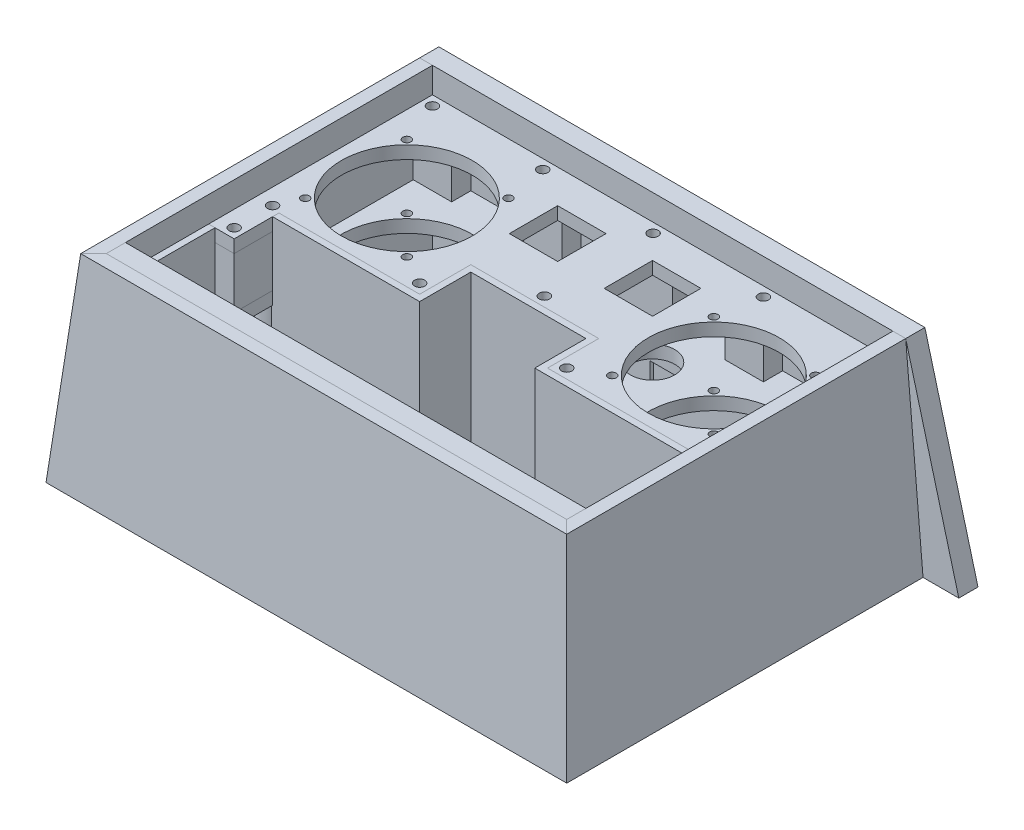
SolidWorks part; units mm, degrees
material "Alum Plate"
ref_plane "Front Plane" through (0, 0, 0) normal (0, 0, 1) x (1, 0, 0)
ref_plane "Top Plane" through (0, 0, 0) normal (0, 1, 0) x (1, 0, 0)
ref_plane "Right Plane" through (0, 0, 0) normal (1, 0, 0) x (0, 0, -1)
other "Center of Mass"
sketch "Sketch1" plane through (0, 0, 0) normal (0, 1, 0) x (1, 0, 0)
  line L0 (-76.2, 25.4) -> (-23.5486, 47.625) construction
  line L1 (114.3, -76.2) -> (-114.3, -76.2)
  line L2 (114.3, -76.2) -> (114.3, 76.2)
  line L3 (114.3, 76.2) -> (-114.3, 76.2)
  line L4 (-114.3, -76.2) -> (-114.3, 76.2)
  line L5 (114.3, -76.2) -> (-114.3, 76.2) construction
  line L6 (114.3, 76.2) -> (-114.3, -76.2) construction
  line L8 (-127, 0) -> (49.8373, 0) construction
  line L9 (0, 0) -> (0, 61.2225) construction
  line L10 (-114.3, -12.7) -> (114.3, -12.7) construction
  line L11 (-111.125, -59.275) -> (-53.975, -59.275)
  line L12 (-111.125, -59.275) -> (-111.125, -23.275)
  line L13 (-111.125, -23.275) -> (-53.975, -23.275)
  line L14 (-53.975, -59.275) -> (-53.975, -23.275)
  line L15 (-111.125, -59.275) -> (-53.975, -23.275) construction
  line L16 (-111.125, -23.275) -> (-53.975, -59.275) construction
  line L17 (-53.975, -55.275) -> (-6.985, -55.275)
  line L18 (-53.975, -55.275) -> (-53.975, -27.275)
  line L19 (-53.975, -27.275) -> (-6.985, -27.275)
  line L20 (-6.985, -55.275) -> (-6.985, -27.275)
  line L21 (-53.975, -55.275) -> (-6.985, -27.275) construction
  line L22 (-53.975, -27.275) -> (-6.985, -55.275) construction
  line L23 (-76.2, -12.7) -> (-76.2, 25.4) construction
  line L24 (-76.2, 25.4) -> (-76.2, 76.2) construction
  circle A0 centre (-76.2, 25.4) radius 32.5
  circle A1 centre (-23.5486, 47.625) radius 10.9728
  point P2 (0, 0)
  point P10 (107.95, -67.76)
  point P11 (-69.85, 31.4275)
  point P15 (-82.55, -41.275)
  point P21 (-76.2, 57.9)
  point P22 (-30.48, -41.275)
  point P27 (-76.2, -7.1)
  point P28 (-23.5486, 36.6522)
  point P29 (-53.975, -41.275)
  point P30 (-23.5486, 58.5978)
  dimension "D1" = 65
  dimension "D6" = 38.1
  dimension "D7" = 21.9456
  dimension "D2" = 50.8
  dimension "D3" = 38.1
  dimension "D4" = 228.6
  dimension "D5" = 63.5
  dimension "D8" = 57.15
  dimension "D10" = 28.575
  dimension "D11" = 36
  dimension "D12" = 57.15
  dimension "D13" = 46.99
  dimension "D14" = 28
  dimension "D15" = 28.575
  dimension "D16" = 3.175
sketch "Sketch2" plane through (0, 0, 0) normal (1, 0, 0) x (0, 0, -1)
  line L0 (-200000, 0) -> (200061.2225, 0) construction
  line L1 (25.4, 50.8) -> (25.4, 53.975) construction
  line L2 (-7.1, 60.975) -> (57.9, 60.975)
  line L3 (-7.1, 60.975) -> (-7.1, 53.975)
  line L4 (-7.1, 53.975) -> (57.9, 53.975)
  line L5 (57.9, 60.975) -> (57.9, 53.975)
  line L6 (-7.1, 60.975) -> (57.9, 53.975) construction
  line L7 (-7.1, 53.975) -> (57.9, 60.975) construction
  line L8 (-7.1, 92.075) -> (57.9, 92.075)
  line L9 (-7.1, 92.075) -> (-7.1, 85.075)
  line L10 (-7.1, 85.075) -> (57.9, 85.075)
  line L11 (57.9, 92.075) -> (57.9, 85.075)
  line L12 (-7.1, 92.075) -> (57.9, 85.075) construction
  line L13 (-7.1, 85.075) -> (57.9, 92.075) construction
  line L14 (23.1368, 73.025) -> (44.1892, 73.025) construction
  line L15 (25.4, 60.975) -> (25.4, 73.025) construction
  line L16 (25.4, 73.025) -> (25.4, 85.075) construction
  line L17 (-59.275, 0) -> (-23.275, 0) construction
  circle A0 centre (25.4, 25.4) radius 25.4
  circle A1 centre (-41.275, 28.575) radius 18
  point P4 (25.4, 57.475)
  point P9 (25.4, 88.575)
  point P26 (-36.2764, 48.644)
  point P27 (0, 0)
  point P30 (-41.275, 0)
  point P31 (-41.275, 28.575)
  dimension "D1" = 50.8
  dimension "D6" = 36
  dimension "D2" = 7
  dimension "D3" = 3.175
  dimension "D4" = 38.1
  dimension "D5" = 25.4
ref_plane "Plane1" through (0, 53.975, 0) normal (0, 1, 0) x (1, 0, 0)
sketch "Sketch3" plane through (0, 53.975, 0) normal (0, 1, 0) x (1, 0, 0)
  line L0 (0, -200000) -> (0, 200061.2225) construction
  line L1 (-114.3, 76.2) -> (0, 76.2)
  line L2 (-114.3, 76.2) -> (-114.3, -12.7)
  line L3 (-114.3, -12.7) -> (0, -12.7)
  line L4 (0, 76.2) -> (0, -12.7)
  line L5 (-114.3, 76.2) -> (0, -12.7) construction
  line L6 (-114.3, -12.7) -> (0, 76.2) construction
  line L7 (-114.3, 25.4) -> (-76.2, 25.4) construction
  line L8 (-114.3, -12.7) -> (114.3, -12.7) construction
  line L9 (-114.3, -76.2) -> (-114.3, 76.2) construction
  circle A0 centre (-76.2, 25.4) radius 32.5 construction
  circle A1 centre (-76.2, 25.4) radius 32.5
  point P7 (-57.15, 31.75)
  point P12 (0, -12.7)
  point P15 (-114.3, 25.4)
extrude "Boss-Extrude1" add sketch "Sketch3" along normal blind 6.35
ref_plane "Plane2" through (0, 73.025, 0) normal (0, 1, 0) x (1, 0, 0)
sketch "Sketch12" plane through (0, 60.325, 0) normal (0, 1, 0) x (1, 0, 0)
  line L0 (-114.3, 76.2) -> (-114.3, -12.7) construction
  line L1 (-114.3, -12.7) -> (-101.6, -12.7)
  line L2 (-114.3, -12.7) -> (-114.3, -34.925)
  line L3 (-114.3, -34.925) -> (-101.6, -34.925)
  line L4 (-101.6, -12.7) -> (-101.6, -34.925)
  line L5 (-114.3, -12.7) -> (-101.6, -34.925) construction
  line L6 (-114.3, -34.925) -> (-101.6, -12.7) construction
  line L7 (-114.3, -12.7) -> (0, -12.7) construction
  point P4 (-107.95, -23.8125)
  point P7 (-101.6, -76.2)
  point P8 (-101.6, -37.9407)
  dimension "D1" = 12.7
  dimension "D2" = 22.225
extrude "Boss-Extrude8" add sketch "Sketch12" against normal up to surface (6.35 mm away) up to face at (-57.15, 53.975, -31.75)
mirror "Mirror1" about plane through (0, 73.025, 0) normal (0, 1, 0) of bodies 128 101
mirror "Mirror2" about plane through (0, 0, 0) normal (1, 0, 0) of bodies 128 102 101 114
sketch "Sketch5" plane through (0, 60.325, 0) normal (0, 1, 0) x (1, 0, 0)
  circle A1 centre (-23.5486, 47.625) radius 10.9728 construction
  circle A3 centre (-23.5486, 47.625) radius 10.9728
  point P6 (0, 25.4)
extrude "Cut-Extrude1" cut sketch "Sketch5" against normal through all
sketch "Sketch47" plane through (0, 92.075, 0) normal (0, 1, 0) x (1, 0, 0)
  line L1 (-35.5486, 59.625) -> (-11.5486, 59.625)
  line L2 (-35.5486, 59.625) -> (-35.5486, 35.625)
  line L3 (-35.5486, 35.625) -> (-11.5486, 35.625)
  line L4 (-11.5486, 59.625) -> (-11.5486, 35.625)
  line L5 (-35.5486, 59.625) -> (-11.5486, 35.625) construction
  line L6 (-35.5486, 35.625) -> (-11.5486, 59.625) construction
  circle A0 centre (-23.5486, 47.625) radius 10.9728 construction
  point P0 (-23.5486, 47.625)
  dimension "D1" = 24
extrude "Cut-Extrude19" cut sketch "Sketch47" against normal up to surface (6.35 mm away)
ref_axis "Axis1" through (0, 60.975, -25.4) along (0, 1, 0)
sketch "Sketch22" plane through (0, 92.075, 0) normal (0, 1, 0) x (1, 0, 0)
  line L0 (-54.1171, 47.4829) -> (-53.219, 48.381) construction
  line L1 (-50.974, 50.626) -> (-101.426, 50.626) construction
  line L2 (-50.974, 50.626) -> (-50.974, 0.174) construction
  line L3 (-50.974, 0.174) -> (-101.426, 0.174) construction
  line L4 (-101.426, 50.626) -> (-101.426, 0.174) construction
  line L5 (-50.974, 50.626) -> (-101.426, 0.174) construction
  line L6 (-50.974, 0.174) -> (-101.426, 50.626) construction
  circle A0 centre (-101.426, 50.626) radius 2.0193
  circle A1 centre (-50.974, 50.626) radius 2.0193
  circle A2 centre (-50.974, 0.174) radius 2.0193
  circle A3 centre (-101.426, 0.174) radius 2.0193
  circle A4 centre (-50.974, 50.626) radius 4.445 construction
  circle A5 centre (-76.2, 25.4) radius 32.5 construction
  point P0 (-76.2, 25.4)
  dimension "D1" = 4.0386
  dimension "D2" = 8.89
  dimension "D3" = 1.27
extrude "Cut-Extrude7" cut sketch "Sketch22" against normal through all
sketch "Sketch51" plane through (0, 92.075, 0) normal (0, 1, 0) x (1, 0, 0)
  line L0 (-114.3, -11.1125) -> (-106.3625, -11.1125) construction
  line L1 (-114.3, -76.2) -> (-114.3, 76.2) construction
  line L2 (-106.3625, -11.1125) -> (-106.3625, -30.1625) construction
  line L3 (-106.3625, -30.1625) -> (-106.3625, -34.925) construction
  line L4 (-101.6, -34.925) -> (-114.3, -34.925) construction
  line L5 (-101.6, -12.7) -> (-101.6, -34.925) construction
  circle A0 centre (-106.3625, -30.1625) radius 2.5527
  circle A1 centre (-106.3625, -11.1125) radius 2.5527
  dimension "D4" = 5.1054
  dimension "D1" = 4.7625
  dimension "D2" = 4.7625
  dimension "D3" = 19.05
extrude "Cut-Extrude20" cut sketch "Sketch51" against normal through all
mirror "Mirror8" about plane through (0, 0, 0) normal (1, 0, 0) of "Cut-Extrude20", "Cut-Extrude7", "Cut-Extrude1", "Cut-Extrude19"
ref_axis "Axis2" through (0, 0.7302, 0) along (0, 1, 0)
sketch "Sketch18" plane through (0, 92.075, 0) normal (0, 1, 0) x (1, 0, 0)
  line L0 (-114.3, 76.2) -> (-114.3, -34.925) construction
  line L1 (114.3, 76.2) -> (-114.3, 76.2) construction
  line L2 (114.3, 76.2) -> (114.3, -34.925) construction
  line L4 (0, 71.4375) -> (0, 0) construction
  line L6 (-109.5375, 71.4375) -> (-54.7687, 71.4375) construction
  line L7 (-54.7687, 71.4375) -> (0, 71.4375) construction
  line L8 (0, 71.4375) -> (54.7687, 71.4375) construction
  line L9 (54.7687, 71.4375) -> (109.5375, 71.4375) construction
  circle A0 centre (-109.5375, 71.4375) radius 4.7625 construction
  circle A1 centre (109.5375, 71.4375) radius 4.7625 construction
  circle A2 centre (0, 71.4375) radius 4.7625 construction
  circle A5 centre (-76.2, 25.4) radius 38.1 construction
  circle A6 centre (76.2, 25.4) radius 38.1 construction
  circle A7 centre (-54.7687, 71.4375) radius 2.5527
  circle A8 centre (-109.5375, 71.4375) radius 2.5527
  circle A9 centre (0, 71.4375) radius 2.5527
  circle A10 centre (109.5375, 71.4375) radius 2.5527
  circle A13 centre (54.7687, 71.4375) radius 2.5527
  dimension "D1" = 9.525
  dimension "D2" = 76.2
  dimension "D3" = 5.1054
extrude "Cut-Extrude5" cut sketch "Sketch18" against normal through all both and the other way through all
sketch "Sketch19" plane through (0, 92.075, 0) normal (0, 1, 0) x (1, 0, 0)
  line L0 (-101.6, -12.7) -> (101.6, -12.7) construction
  line L1 (-31.75, -12.7) -> (31.75, -12.7)
  line L2 (-31.75, -12.7) -> (-31.75, 12.7)
  line L3 (-31.75, 12.7) -> (31.75, 12.7)
  line L4 (31.75, -12.7) -> (31.75, 12.7)
  line L5 (-31.75, -12.7) -> (31.75, 12.7) construction
  line L6 (-31.75, 12.7) -> (31.75, -12.7) construction
  line L8 (-114.3, -12.7) -> (114.3, -12.7) construction
  line L9 (114.3, 76.2) -> (-114.3, 76.2) construction
  line L10 (0, -200000) -> (0, 200061.2225) construction
  circle A0 centre (-36.5125, -7.9375) radius 2.5527
  circle A1 centre (-36.5125, -7.9375) radius 4.7625 construction
  circle A2 centre (36.5125, -7.9375) radius 2.5527
  circle A3 centre (36.5125, -7.9375) radius 4.7625 construction
  circle A4 centre (0, 17.4625) radius 4.7625 construction
  circle A5 centre (0, 17.4625) radius 2.5527
  point P4 (0, 0)
  dimension "D3" = 9.525
  dimension "D4" = 5.1054
  dimension "D1" = 63.5
  dimension "D2" = 63.5
extrude "Cut-Extrude6" cut sketch "Sketch19" against normal through all both and the other way through all
sketch "Sketch48" plane through (0, 60.325, 0) normal (0, 1, 0) x (1, 0, 0)
  line L0 (114.3, 76.2) -> (-114.3, 76.2) construction
  line L1 (-114.3, 76.2) -> (-95.25, 76.2)
  line L2 (-114.3, 76.2) -> (-114.3, 66.675)
  line L3 (-114.3, 66.675) -> (-95.25, 66.675)
  line L4 (-95.25, 76.2) -> (-95.25, 66.675)
  line L5 (-114.3, 76.2) -> (-95.25, 66.675) construction
  line L6 (-114.3, 66.675) -> (-95.25, 76.2) construction
  line L7 (-59.5312, 76.2) -> (-40.4812, 76.2)
  line L8 (-59.5312, 76.2) -> (-59.5312, 66.675)
  line L9 (-59.5312, 66.675) -> (-40.4812, 66.675)
  line L10 (-40.4812, 76.2) -> (-40.4812, 66.675)
  line L11 (-59.5312, 76.2) -> (-40.4812, 66.675) construction
  line L12 (-59.5312, 66.675) -> (-40.4812, 76.2) construction
  line L14 (-14.2875, 76.2) -> (14.2875, 76.2)
  line L15 (-14.2875, 76.2) -> (-14.2875, 66.675)
  line L16 (-14.2875, 66.675) -> (14.2875, 66.675)
  line L17 (14.2875, 76.2) -> (14.2875, 66.675)
  line L18 (-14.2875, 76.2) -> (14.2875, 66.675) construction
  line L19 (-14.2875, 66.675) -> (14.2875, 76.2) construction
  line L20 (40.4812, 76.2) -> (59.5312, 76.2)
  line L21 (40.4812, 76.2) -> (40.4812, 66.675)
  line L22 (40.4812, 66.675) -> (59.5312, 66.675)
  line L23 (59.5312, 76.2) -> (59.5312, 66.675)
  line L24 (40.4812, 76.2) -> (59.5312, 66.675) construction
  line L25 (40.4812, 66.675) -> (59.5312, 76.2) construction
  line L26 (114.3, 76.2) -> (95.25, 76.2)
  line L27 (114.3, 76.2) -> (114.3, 66.675)
  line L28 (114.3, 66.675) -> (95.25, 66.675)
  line L29 (95.25, 76.2) -> (95.25, 66.675)
  line L30 (114.3, 76.2) -> (95.25, 66.675) construction
  line L31 (114.3, 66.675) -> (95.25, 76.2) construction
  circle A0 centre (-54.7687, 71.4375) radius 2.5527 construction
  circle A1 centre (54.7687, 71.4375) radius 2.5527 construction
  circle A2 centre (109.5375, 71.4375) radius 2.5527 construction
  circle A3 centre (0, 71.4375) radius 2.5527 construction
  circle A4 centre (-109.5375, 71.4375) radius 2.5527 construction
  circle A5 centre (109.5375, 71.4375) radius 2.5527
  circle A6 centre (54.7687, 71.4375) radius 2.5527
  circle A7 centre (0, 71.4375) radius 2.5527
  circle A8 centre (-54.7687, 71.4375) radius 2.5527
  circle A9 centre (-109.5375, 71.4375) radius 2.5527
  point P4 (-104.775, 71.4375)
  point P10 (-50.0062, 71.4375)
  point P17 (0, 71.4375)
  point P22 (50.0062, 71.4375)
  point P27 (104.775, 71.4375)
  point P29 (0, 0)
  point P30 (0, 69.85)
  point P32 (0, 69.85)
  point P36 (60.129, 63.5)
  dimension "D4" = 4.7625
  dimension "D1" = 19.05
  dimension "D2" = 4.7625
  dimension "D3" = 28.575
extrude "Boss-Extrude9" add sketch "Sketch48" along normal up to surface (25.4 mm away) separate body
sketch "Sketch52" plane through (0, 60.325, 0) normal (0, 1, 0) x (1, 0, 0)
  line L0 (-101.6, -34.925) -> (-101.6, -12.7) construction
  line L1 (-101.6, -34.925) -> (-111.125, -34.925)
  line L2 (-101.6, -34.925) -> (-101.6, -6.35)
  line L3 (-101.6, -6.35) -> (-111.125, -6.35)
  line L4 (-111.125, -34.925) -> (-111.125, -6.35)
  line L5 (-101.6, -34.925) -> (-111.125, -6.35) construction
  line L6 (-101.6, -6.35) -> (-111.125, -34.925) construction
  line L7 (-114.3, 76.2) -> (-114.3, -34.925) construction
  circle A0 centre (-106.3625, -11.1125) radius 2.5527 construction
  circle A3 centre (-106.3625, -30.1625) radius 2.5527 construction
  circle A6 centre (-106.3625, -30.1625) radius 2.5527
  circle A7 centre (-106.3625, -11.1125) radius 2.5527
  point P4 (-106.3625, -20.6375)
  dimension "D1" = 4.7625
  dimension "D2" = 3.175
extrude "Boss-Extrude11" add sketch "Sketch52" along normal up to surface (25.4 mm away) separate body
sketch "Sketch53" plane through (-111.125, 0, 0) normal (-1, 0, 0) x (0, 0, 1)
  line L0 (34.925, 92.075) -> (34.925, 85.725)
  line L1 (34.925, 85.725) -> (6.35, 85.725)
  line L2 (6.35, 85.725) -> (6.35, 60.325)
  line L3 (6.35, 60.325) -> (15.875, 60.325)
  line L4 (-76.2, 60.325) -> (34.925, 60.325) construction
  line L5 (15.875, 60.325) -> (15.875, 53.975)
  line L6 (-76.2, 53.975) -> (34.925, 53.975) construction
  line L7 (15.875, 53.975) -> (15.875, 47.625)
  line L8 (15.875, 47.625) -> (76.2, 47.625)
  line L9 (76.2, 47.625) -> (76.2, 92.075)
  line L10 (76.2, 92.075) -> (34.925, 92.075)
  dimension "D1" = 9.525
  dimension "D2" = 6.35
extrude "Boss-Extrude12" add sketch "Sketch53" along normal blind 3.175 separate body
sketch "Sketch54" plane through (0, 53.975, 0) normal (0, -1, 0) x (1, 0, 0)
  line L0 (114.3, 76.2) -> (114.3, -76.2) construction
  line L1 (-114.3, 15.875) -> (-111.125, 15.875)
  line L2 (-114.3, 15.875) -> (-114.3, 34.925)
  line L3 (-114.3, 34.925) -> (-111.125, 34.925)
  line L4 (-111.125, 15.875) -> (-111.125, 34.925)
  line L5 (-114.3, 15.875) -> (-111.125, 34.925) construction
  line L6 (-114.3, 34.925) -> (-111.125, 15.875) construction
  line L7 (114.3, 15.875) -> (111.125, 15.875)
  line L8 (114.3, 15.875) -> (114.3, 34.925)
  line L9 (114.3, 34.925) -> (111.125, 34.925)
  line L10 (111.125, 15.875) -> (111.125, 34.925)
  line L11 (114.3, 15.875) -> (111.125, 34.925) construction
  line L12 (114.3, 34.925) -> (111.125, 15.875) construction
  line L13 (101.6, 34.925) -> (114.3, 34.925) construction
  point P4 (-112.7125, 25.4)
  point P11 (112.7125, 25.4)
extrude "Cut-Extrude21" cut sketch "Sketch54" against normal through all
sketch "Sketch56" plane through (-114.3, 0, 0) normal (-1, 0, 0) x (0, 0, 1)
  line L0 (15.875, 47.625) -> (15.875, 9.525)
  line L1 (15.875, 9.525) -> (76.2, 9.525)
  line L2 (76.2, 9.525) -> (76.2, 47.625)
  line L3 (15.875, 47.625) -> (76.2, 47.625)
  line L4 (26.035, 43.815) -> (56.515, 43.815) construction
  line L5 (26.035, 43.815) -> (26.035, 13.335) construction
  line L6 (26.035, 13.335) -> (56.515, 13.335) construction
  line L7 (56.515, 43.815) -> (56.515, 13.335) construction
  line L8 (26.035, 43.815) -> (56.515, 13.335) construction
  line L9 (26.035, 13.335) -> (56.515, 43.815) construction
  circle A0 centre (26.035, 43.815) radius 1.5875
  circle A1 centre (56.515, 43.815) radius 1.5875
  circle A2 centre (56.515, 13.335) radius 1.5875
  circle A3 centre (26.035, 13.335) radius 1.5875
  circle A4 centre (41.275, 28.575) radius 9.525
  point P3 (41.275, 28.575)
  dimension "D2" = 3.175
  dimension "D4" = 19.05
  dimension "D1" = 19.05
  dimension "D3" = 30.48
extrude "Boss-Extrude14" add sketch "Sketch56" against normal up to surface (3.175 mm away) up to face at (-111.125, 71.4375, 33.3375)
mirror "Mirror9" about plane through (0, 0, 0) normal (1, 0, 0) of bodies 211 204 206
sketch "Sketch55" plane through (0, 0, 76.2) normal (0, 0, 1) x (1, 0, 0)
  line L0 (-101.6, 92.075) -> (-114.3, 92.075) construction
  line L1 (-114.3, 104.775) -> (114.3, 104.775)
  line L2 (-114.3, 104.775) -> (-114.3, 28.575)
  line L3 (-114.3, 28.575) -> (114.3, 28.575)
  line L4 (114.3, 104.775) -> (114.3, 28.575)
  line L5 (-114.3, 104.775) -> (114.3, 28.575) construction
  line L6 (-114.3, 28.575) -> (114.3, 104.775) construction
  line L7 (114.3, 9.525) -> (114.3, 92.075) construction
  line L8 (-111.125, 9.525) -> (-114.3, 9.525) construction
  point P4 (0, 66.675)
  point P7 (114.3, 9.525)
  point P9 (-120.2712, 111.6306)
  point P13 (114.3, 23.4214)
  point P18 (-112.7125, 9.525)
  dimension "D1" = 12.7
  dimension "D2" = 19.05
extrude "Boss-Extrude13" add sketch "Sketch55" along normal blind 9.525 separate body
sketch "Sketch57" plane through (0, 0, -76.2) normal (0, 0, -1) x (-1, 0, 0)
  line L0 (-120.65, 104.775) -> (120.65, 104.775)
  line L1 (120.65, 104.775) -> (147.0229, 6.35)
  line L2 (147.0229, 6.35) -> (-147.0229, 6.35)
  line L3 (-147.0229, 6.35) -> (-120.65, 104.775)
  line L4 (200127, 0) -> (-200049.8373, 0) construction
  line L5 (-114.3, 85.725) -> (-114.3, 92.075) construction
  line L6 (-114.3, 104.775) -> (114.3, 104.775) construction
  line L7 (114.3, 85.725) -> (114.3, 92.075) construction
  point P2 (-120.65, 81.8586)
  point P10 (135.2249, 92.3982)
  point P11 (-127.2615, 118.0162)
  point P12 (-120.65, 101.2944)
  dimension "D1" = 6.35
  dimension "D2" = 15
  dimension "D3" = 6.35
  dimension "D4" = 6.35
extrude "Boss-Extrude15" add sketch "Sketch57" along normal blind 9.525 separate body
sketch "Sketch58" plane through (0, 0, -76.2) normal (0, 0, 1) x (1, 0, 0)
  line L0 (-129.2611, 6.35) -> (-120.65, 104.775)
  line L1 (-120.65, 104.775) -> (-114.3, 104.775)
  line L2 (-114.3, 104.775) -> (-114.3, 6.35)
  line L3 (147.0229, 6.35) -> (-147.0229, 6.35) construction
  line L4 (-114.3, 6.35) -> (-129.2611, 6.35)
  point P9 (-131.1627, 6.35)
  dimension "D1" = 5
sketch "Sketch59" plane through (0, 104.775, 0) normal (0, 1, 0) x (1, 0, 0)
  line L0 (-114.3, 76.2) -> (-114.3, -85.725)
  line L1 (-114.3, -85.725) -> (114.3, -85.725)
  line L2 (114.3, -85.725) -> (114.3, 76.2)
sketch "Sketch66" plane through (0, 0, 85.725) normal (0, 0, 1) x (1, 0, 0)
  line L0 (0, 28.575) -> (0, 66.675) construction
  line L1 (-114.3, 28.575) -> (114.3, 28.575) construction
  line L2 (0, 66.675) -> (0, 104.775) construction
  line L3 (114.3, 104.775) -> (-114.3, 104.775) construction
  line L4 (16.4978, 57.15) -> (8.2489, 61.9125) construction
  line L5 (5.4993, 57.15) -> (10.9985, 66.675)
  line L6 (10.9985, 66.675) -> (5.4993, 76.2)
  line L7 (5.4993, 76.2) -> (-5.4993, 76.2)
  line L8 (-5.4993, 76.2) -> (-10.9985, 66.675)
  line L9 (-10.9985, 66.675) -> (-5.4993, 57.15)
  line L10 (-5.4993, 57.15) -> (5.4993, 57.15)
  line L11 (19.2474, 61.9125) -> (13.7482, 52.3875)
  line L12 (13.7482, 52.3875) -> (19.2474, 42.8625)
  line L13 (19.2474, 42.8625) -> (30.2459, 42.8625)
  line L14 (30.2459, 42.8625) -> (35.7452, 52.3875)
  line L15 (35.7452, 52.3875) -> (30.2459, 61.9125)
  line L16 (30.2459, 61.9125) -> (19.2474, 61.9125)
  line L17 (30.2459, 71.4375) -> (35.7452, 80.9625)
  line L18 (35.7452, 80.9625) -> (30.2459, 90.4875)
  line L19 (30.2459, 90.4875) -> (19.2474, 90.4875)
  line L20 (19.2474, 90.4875) -> (13.7482, 80.9625)
  line L21 (13.7482, 80.9625) -> (19.2474, 71.4375)
  line L22 (19.2474, 71.4375) -> (30.2459, 71.4375)
  line L23 (8.2489, 71.4375) -> (16.4978, 76.2) construction
  line L24 (24.7467, 71.4375) -> (24.7467, 61.9125) construction
  line L25 (68.7408, 61.9125) -> (63.2415, 52.3875)
  line L32 (63.2415, 52.3875) -> (68.7408, 42.8625)
  line L33 (68.7408, 42.8625) -> (79.7393, 42.8625)
  line L34 (79.7393, 42.8625) -> (85.2386, 52.3875)
  line L35 (85.2386, 52.3875) -> (79.7393, 61.9125)
  line L36 (79.7393, 61.9125) -> (68.7408, 61.9125)
  line L37 (79.7393, 71.4375) -> (85.2386, 80.9625)
  line L38 (85.2386, 80.9625) -> (79.7393, 90.4875)
  line L39 (79.7393, 90.4875) -> (68.7408, 90.4875)
  line L40 (68.7408, 90.4875) -> (63.2415, 80.9625)
  line L41 (63.2415, 80.9625) -> (68.7408, 71.4375)
  line L42 (68.7408, 71.4375) -> (79.7393, 71.4375)
  line L43 (54.9926, 57.15) -> (60.4919, 66.675)
  line L44 (60.4919, 66.675) -> (54.9926, 76.2)
  line L45 (54.9926, 76.2) -> (43.9941, 76.2)
  line L46 (43.9941, 76.2) -> (38.4948, 66.675)
  line L47 (38.4948, 66.675) -> (43.9941, 57.15)
  line L48 (43.9941, 57.15) -> (54.9926, 57.15)
  line L49 (32.9956, 76.2) -> (41.2445, 71.4375) construction
  line L50 (-79.7393, 61.9125) -> (-68.7408, 61.9125)
  line L51 (-85.2386, 52.3875) -> (-79.7393, 61.9125)
  line L52 (-79.7393, 42.8625) -> (-85.2386, 52.3875)
  line L53 (-68.7408, 42.8625) -> (-79.7393, 42.8625)
  line L54 (-63.2415, 52.3875) -> (-68.7408, 42.8625)
  line L55 (-68.7408, 61.9125) -> (-63.2415, 52.3875)
  line L56 (-68.7408, 71.4375) -> (-79.7393, 71.4375)
  line L57 (-63.2415, 80.9625) -> (-68.7408, 71.4375)
  line L58 (-68.7408, 90.4875) -> (-63.2415, 80.9625)
  line L59 (-79.7393, 90.4875) -> (-68.7408, 90.4875)
  line L60 (-85.2386, 80.9625) -> (-79.7393, 90.4875)
  line L61 (-79.7393, 71.4375) -> (-85.2386, 80.9625)
  line L62 (-43.9941, 57.15) -> (-54.9926, 57.15)
  line L63 (-38.4948, 66.675) -> (-43.9941, 57.15)
  line L64 (-43.9941, 76.2) -> (-38.4948, 66.675)
  line L65 (-54.9926, 76.2) -> (-43.9941, 76.2)
  line L66 (-60.4919, 66.675) -> (-54.9926, 76.2)
  line L67 (-54.9926, 57.15) -> (-60.4919, 66.675)
  line L68 (-19.2474, 71.4375) -> (-30.2459, 71.4375)
  line L69 (-13.7482, 80.9625) -> (-19.2474, 71.4375)
  line L70 (-19.2474, 90.4875) -> (-13.7482, 80.9625)
  line L71 (-30.2459, 90.4875) -> (-19.2474, 90.4875)
  line L72 (-35.7452, 80.9625) -> (-30.2459, 90.4875)
  line L73 (-30.2459, 71.4375) -> (-35.7452, 80.9625)
  line L74 (-30.2459, 61.9125) -> (-19.2474, 61.9125)
  line L75 (-35.7452, 52.3875) -> (-30.2459, 61.9125)
  line L76 (-30.2459, 42.8625) -> (-35.7452, 52.3875)
  line L77 (-19.2474, 42.8625) -> (-30.2459, 42.8625)
  line L78 (-13.7482, 52.3875) -> (-19.2474, 42.8625)
  line L79 (-19.2474, 61.9125) -> (-13.7482, 52.3875)
  circle A0 centre (0, 66.675) radius 9.525 construction
  circle A1 centre (24.7467, 52.3875) radius 9.525 construction
  circle A2 centre (24.7467, 80.9625) radius 9.525 construction
  dimension "D1" = 19.05
  dimension "D2" = 9.525
  dimension "D3" = 2
extrude "Cut-Extrude23" cut sketch "Sketch66" against normal through all
sweep "Sweep1" add profiles "Sketch58" path "Sketch59"
sketch "Sketch60" plane through (-114.3, 0, 0) normal (1, 0, 0) x (0, 0, -1)
  line L0 (-85.725, 28.575) -> (-76.2, 28.575)
  line L1 (-76.2, 28.575) -> (-76.2, 9.525)
  line L2 (-76.2, 9.525) -> (-15.875, 9.525)
  line L3 (-15.875, 9.525) -> (-15.875, 53.975)
  line L4 (-15.875, 53.975) -> (-9.525, 53.975)
  line L5 (-9.525, 53.975) -> (-9.525, 6.35)
  line L6 (76.2, 6.35) -> (-85.725, 6.35) construction
  line L7 (-9.525, 6.35) -> (-85.725, 6.35)
  line L8 (-85.725, 6.35) -> (-85.725, 28.575)
  dimension "D1" = 6.35
extrude "Boss-Extrude16" add sketch "Sketch60" along normal up to surface (3.175 mm away) separate body up to face at (-111.125, 61.9125, 33.3375)
sketch "Sketch61" plane through (0, 28.575, 0) normal (0, -1, 0) x (1, 0, 0)
  line L0 (114.3, 76.2) -> (-114.3, 76.2) construction
  line L1 (-111.125, 85.725) -> (0, 85.725)
  line L2 (-111.125, 85.725) -> (-111.125, 76.2)
  line L3 (-111.125, 76.2) -> (0, 76.2)
  line L4 (0, 85.725) -> (0, 76.2)
  line L5 (-111.125, 85.725) -> (0, 76.2) construction
  line L6 (-111.125, 76.2) -> (0, 85.725) construction
  point P4 (-55.5625, 80.9625)
  point P8 (-111.125, 85.725)
extrude "Boss-Extrude17" add sketch "Sketch61" along normal up to surface (22.225 mm away) separate body up to face at (-121.7805, 6.35, 8.5028)
sketch "Sketch62" plane through (0, 53.975, 0) normal (0, -1, 0) x (1, 0, 0)
  line L0 (-106.3625, 4.7625) -> (-114.3, 4.7625)
  line L1 (-114.3, 76.2) -> (-114.3, -76.2) construction
  line L2 (-114.3, 4.7625) -> (-114.3, 15.875)
  line L3 (-114.3, 15.875) -> (-110.5626, 15.875)
  line L4 (-31.75, 12.7) -> (-100.2141, 12.7)
  line L5 (-114.3, 12.7) -> (114.3, 12.7) construction
  line L6 (-31.75, -12.7) -> (-31.75, 12.7) construction
  line L7 (-102.1624, 15.875) -> (-28.575, 15.875)
  line L8 (-31.75, 12.7) -> (-31.75, -12.7)
  line L9 (-31.75, -12.7) -> (0, -12.7)
  line L10 (31.75, -12.7) -> (-31.75, -12.7) construction
  line L11 (0, -12.7) -> (0, -9.525)
  line L12 (0, 200000) -> (0, -200061.2225) construction
  line L13 (0, -9.525) -> (-28.575, -9.525)
  line L14 (-28.575, -9.525) -> (-28.575, 15.875)
  line L15 (-31.75, 15.875) -> (-31.75, 12.7) construction
  line L16 (-28.575, -9.525) -> (-28.575, -12.7) construction
  line L17 (-31.75, 12.7) -> (-28.575, 12.7) construction
  arc A0 (-106.3625, 4.7625) -> (-100.2141, 12.7) centre (-106.3625, 11.1125) ccw
  circle A1 centre (-106.3625, 11.1125) radius 4.7625
  arc A2 (-110.5626, 15.875) -> (-106.3625, 4.7625) centre (-106.3625, 11.1125) ccw construction
  arc A3 (-100.2141, 12.7) -> (-102.1624, 15.875) centre (-106.3625, 11.1125) ccw construction
  arc A4 (-102.1624, 15.875) -> (-110.5626, 15.875) centre (-106.3625, 11.1125) ccw
  point P18 (-111.3098, 15.0933)
  dimension "D1" = 9.525
  dimension "D2" = 12.7
  dimension "D3" = 3.175
extrude "Boss-Extrude18" add sketch "Sketch62" along normal up to surface (47.625 mm away) separate body up to face at (-121.7805, 6.35, 8.5028)
sketch "Sketch63" plane through (0, 53.975, 0) normal (0, 1, 0) x (1, 0, 0)
  line L4 (-101.6, -12.7) -> (-101.6, -15.875)
  line L5 (-28.575, -15.875) -> (-102.1624, -15.875) construction
  line L6 (-101.6, -12.7) -> (-101.6, -34.925) construction
  line L7 (-101.6, -15.875) -> (-28.575, -15.875)
  line L30 (-28.575, -15.875) -> (-28.575, 9.525)
  line L31 (-28.575, 9.525) -> (0, 9.525)
  line L32 (0, 9.525) -> (0, 12.7)
  line L33 (0, 12.7) -> (-31.75, 12.7)
  line L34 (-31.75, 12.7) -> (-31.75, -12.7)
  line L35 (-31.75, -12.7) -> (-101.6, -12.7)
extrude "Boss-Extrude19" add sketch "Sketch63" along normal up to surface (38.1 mm away)
mirror "Mirror14" about plane through (0, 0, 0) normal (1, 0, 0) of bodies 217 216 215 214
combine bodies "Combine1" operation type add bodies to combine 213 220 215 219 216 221 214 217 218
sketch "Sketch64" plane through (0, 6.35, 0) normal (0, -1, 0) x (1, 0, 0)
  line L10 (111.125, 76.2) -> (-111.125, 76.2)
  line L11 (111.125, 15.875) -> (111.125, 76.2)
  line L12 (110.5626, 15.875) -> (111.125, 15.875)
  line L13 (28.575, 15.875) -> (102.1624, 15.875)
  line L14 (28.575, -9.525) -> (28.575, 15.875)
  line L15 (-28.575, -9.525) -> (28.575, -9.525)
  line L16 (-28.575, 15.875) -> (-28.575, -9.525)
  line L17 (-102.1624, 15.875) -> (-28.575, 15.875)
  line L18 (-111.125, 15.875) -> (-110.5626, 15.875)
  line L19 (-111.125, 76.2) -> (-111.125, 15.875)
  line L20 (111.125, 76.2) -> (-111.125, 76.2)
  line L21 (111.125, 15.875) -> (111.125, 76.2)
  line L22 (110.5626, 15.875) -> (111.125, 15.875)
  line L23 (28.575, 15.875) -> (102.1624, 15.875)
  line L24 (28.575, -9.525) -> (28.575, 15.875)
  line L25 (-28.575, -9.525) -> (28.575, -9.525)
  line L26 (-28.575, 15.875) -> (-28.575, -9.525)
  line L27 (-102.1624, 15.875) -> (-28.575, 15.875)
  line L28 (-111.125, 15.875) -> (-110.5626, 15.875)
  line L29 (-111.125, 76.2) -> (-111.125, 15.875)
  arc A6 (110.5626, 15.875) -> (102.1624, 15.875) centre (106.3625, 11.1125) ccw
  arc A7 (-102.1624, 15.875) -> (-110.5626, 15.875) centre (-106.3625, 11.1125) ccw
  arc A8 (110.5626, 15.875) -> (102.1624, 15.875) centre (106.3625, 11.1125) ccw
  arc A9 (-102.1624, 15.875) -> (-110.5626, 15.875) centre (-106.3625, 11.1125) ccw
  dimension "D3" = 0
extrude "Boss-Extrude20" add sketch "Sketch64" against normal blind 6.35
sketch "Sketch65" plane through (-114.3, 0, 0) normal (1, 0, 0) x (0, 0, -1)
  circle A0 centre (-41.275, 28.575) radius 18 construction
  circle A1 centre (-41.275, 28.575) radius 18 construction
  circle A2 centre (-41.275, 28.575) radius 25.4
  dimension "D1" = 50.8
extrude "Cut-Extrude22" cut sketch "Sketch65" against normal through all
sketch "Sketch67" plane through (0, 0, 0) normal (1, 0, 0) x (0, 0, -1)
  line L0 (85.725, 6.35) -> (85.725, 19.05)
  line L1 (85.725, 104.775) -> (85.725, 6.35) construction
  line L2 (85.725, 19.05) -> (78.105, 19.05)
  line L3 (78.105, 19.05) -> (78.105, 31.75)
  line L4 (78.105, 31.75) -> (85.725, 31.75)
  line L5 (85.725, 31.75) -> (85.725, 44.45)
  line L6 (85.725, 44.45) -> (92.075, 44.45)
  line L7 (92.075, 44.45) -> (112.395, 29.21)
  line L8 (85.725, 6.35) -> (104.775, 6.35)
  arc A0 (104.775, 6.35) -> (112.395, 29.21) centre (104.775, 19.05) ccw
  circle A1 centre (104.775, 19.05) radius 4.7625
  point P14 (104.775, 17.0317)
  dimension "D2" = 9.525
  dimension "D8" = 12.7
  dimension "D1" = 6.35
  dimension "D3" = 7.62
  dimension "D4" = 12.7
  dimension "D5" = 12.7
  dimension "D6" = 12.7
  dimension "D7" = 19.05
extrude "Boss-Extrude21" add sketch "Sketch67" along normal mid plane 12.7 separate body
pattern_linear "LPattern1" count 2 spacing 76.2 along (-1, 0, 0) of bodies 226
pattern_linear "LPattern2" count 2 spacing 76.2 along (1, 0, 0) of bodies 226
sketch "Sketch68" plane through (0, 0, -85.725) normal (0, 0, 1) x (1, 0, 0)
  line L0 (69.85, 31.75) -> (69.85, 19.05) construction
  line L1 (69.85, 19.05) -> (82.55, 19.05) construction
  line L2 (82.55, 19.05) -> (82.55, 31.75) construction
  line L3 (82.55, 31.75) -> (69.85, 31.75) construction
  line L4 (-6.35, 31.75) -> (-6.35, 19.05) construction
  line L5 (-6.35, 19.05) -> (6.35, 19.05) construction
  line L6 (6.35, 19.05) -> (6.35, 31.75) construction
  line L7 (6.35, 31.75) -> (-6.35, 31.75) construction
  line L8 (-82.55, 31.75) -> (-82.55, 19.05) construction
  line L9 (-82.55, 19.05) -> (-69.85, 19.05) construction
  line L10 (-69.85, 19.05) -> (-69.85, 31.75) construction
  line L11 (-69.85, 31.75) -> (-82.55, 31.75) construction
  line L12 (69.85, 31.75) -> (69.85, 19.05)
  line L13 (69.85, 19.05) -> (82.55, 19.05)
  line L14 (82.55, 19.05) -> (82.55, 31.75)
  line L15 (82.55, 31.75) -> (69.85, 31.75)
  line L16 (-6.35, 31.75) -> (-6.35, 19.05)
  line L17 (-6.35, 19.05) -> (6.35, 19.05)
  line L18 (6.35, 19.05) -> (6.35, 31.75)
  line L19 (6.35, 31.75) -> (-6.35, 31.75)
  line L20 (-82.55, 31.75) -> (-82.55, 19.05)
  line L21 (-82.55, 19.05) -> (-69.85, 19.05)
  line L22 (-69.85, 19.05) -> (-69.85, 31.75)
  line L23 (-69.85, 31.75) -> (-82.55, 31.75)
extrude "Cut-Extrude24" cut sketch "Sketch68" along normal through all
sketch "Sketch69" plane through (-82.55, 0, 0) normal (-1, 0, 0) x (0, 0, 1)
  circle A0 centre (-104.775, 19.05) radius 4.7625 construction
  circle A1 centre (-104.775, 19.05) radius 4.7625
extrude "Boss-Extrude23" add sketch "Sketch69" against normal offset from surface (177.8 mm away) 6.35 from offset 6.35 separate body up to face at (82.55, 25.5182, -90.7326) offset beyond the face yes
